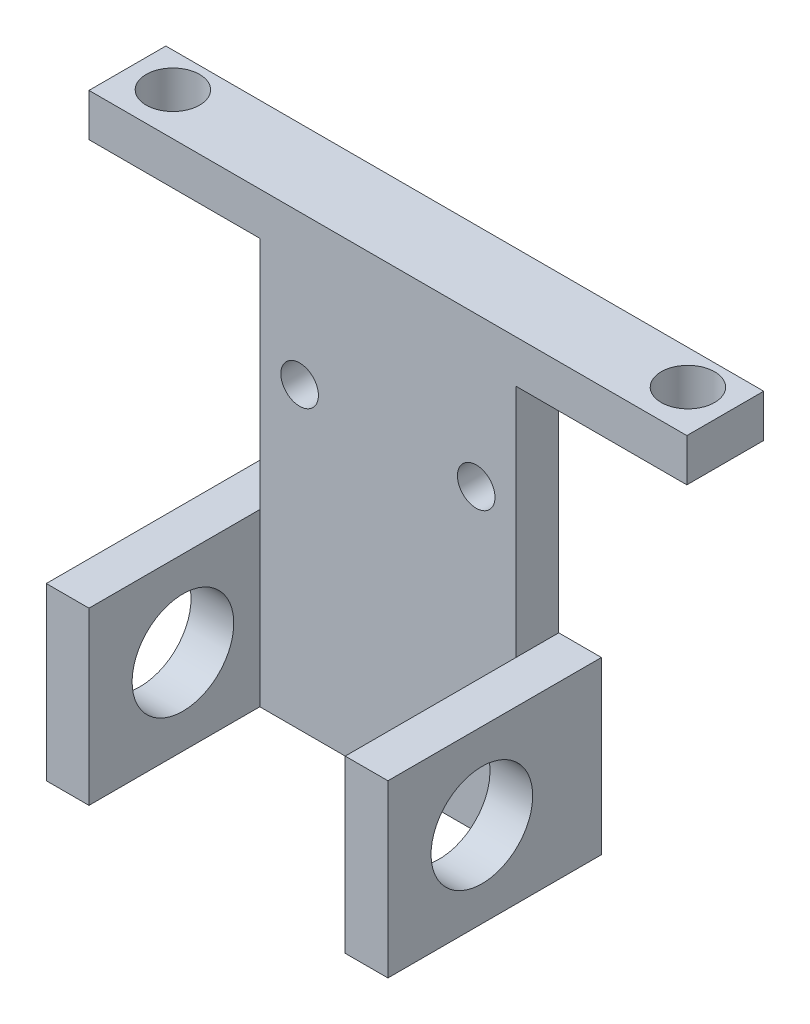
SolidWorks part; units mm, degrees
ref_plane "Front Plane" through (0, 0, 0) normal (0, 0, 1) x (1, 0, 0)
ref_plane "Top Plane" through (0, 0, 0) normal (0, 1, 0) x (1, 0, 0)
ref_plane "Right Plane" through (0, 0, 0) normal (1, 0, 0) x (0, 0, -1)
sketch "Sketch4" plane through (0, 0, 0) normal (0, 1, 0) x (1, 0, 0)
  line L1 (-17.78, 2.286) -> (17.78, 2.286)
  line L2 (-17.78, 2.286) -> (-17.78, -2.286)
  line L3 (-17.78, -2.286) -> (17.78, -2.286)
  line L4 (17.78, 2.286) -> (17.78, -2.286)
  line L5 (-17.78, 2.286) -> (17.78, -2.286) construction
  line L6 (-17.78, -2.286) -> (17.78, 2.286) construction
  point P0 (0, 0)
  dimension "D1" = 35.56
  dimension "D2" = 4.572
extrude "Boss-Extrude3" add sketch "Sketch4" along normal blind 2.54
sketch "Sketch5" plane through (0, 0, 0) normal (0, -1, 0) x (1, 0, 0)
  line L0 (0, -55) -> (0, 55) construction
  line L1 (-17.78, 2.286) -> (17.78, 2.286) construction
  circle A0 centre (-15.3162, -0.2413) radius 1.5875
  circle A1 centre (15.3162, -0.2413) radius 1.5875
  dimension "D1" = 30.6324
  dimension "D2" = 3.175
  dimension "D3" = 2.5273
sketch "Sketch7" plane through (0, -2.032, 2.286) normal (0, 0, -1) x (1, 0, 0)
  line L0 (17.78, -2.032) -> (-17.78, -2.032) construction
  line L1 (7.62, 22.098) -> (-7.62, 22.098)
  line L2 (7.62, 22.098) -> (7.62, -2.032)
  line L3 (7.62, -2.032) -> (-7.62, -2.032)
  line L4 (-7.62, 22.098) -> (-7.62, -2.032)
  line L5 (7.62, 22.098) -> (-7.62, -2.032) construction
  line L6 (7.62, -2.032) -> (-7.62, 22.098) construction
  line L8 (0, -3.429) -> (0, -0.635) construction
  point P0 (0, 10.033)
  dimension "D1" = 24.13
  dimension "D2" = 15.24
extrude "Laser PDB holes" cut sketch "Sketch5" against normal through all
extrude "Boss-Extrude5" add sketch "Sketch7" along normal blind 2.54
sketch "Sketch9" plane through (0, 0, 2.286) normal (0, 0, 1) x (1, 0, 0)
  line L1 (0, -1.397) -> (0, 1.397) construction
  line L2 (2.5146, 0) -> (-2.5146, 0) construction
  circle A0 centre (-5.2514, -6.35) radius 1.1176
  circle A1 centre (5.2514, -6.35) radius 1.1176
  dimension "D1" = 2.2352
  dimension "D2" = 6.35
  dimension "D3" = 10.5029
extrude "Cut-Extrude5" cut sketch "Sketch9" against normal through all
sketch "Sketch10" plane through (7.62, 0, 0) normal (1, 0, 0) x (0, 0, -1)
  line L1 (0.254, -24.13) -> (-12.446, -24.13)
  line L2 (0.254, -24.13) -> (0.254, -13.97)
  line L3 (0.254, -13.97) -> (-12.446, -13.97)
  line L4 (-12.446, -24.13) -> (-12.446, -13.97)
  dimension "D1" = 12.7
  dimension "D2" = 10.16
extrude "Boss-Extrude6" add sketch "Sketch10" along normal blind 2.54
mirror "Mirror1" about plane through (0, 0, 0) normal (1, 0, 0) of "Boss-Extrude6"
sketch "Sketch11" plane through (10.16, 0, 0) normal (1, 0, 0) x (0, 0, -1)
  line L0 (-12.446, -24.13) -> (0.254, -24.13) construction
  line L3 (0.254, -24.13) -> (0.254, -13.97) construction
  circle A0 centre (-6.858, -19.05) radius 3.0226
  point P6 (-12.446, -20.034)
  dimension "D1" = 6.0452
  dimension "D3" = 7.112
  dimension "D2" = 5.08
extrude "Cut-Extrude6" cut sketch "Sketch11" against normal through all
